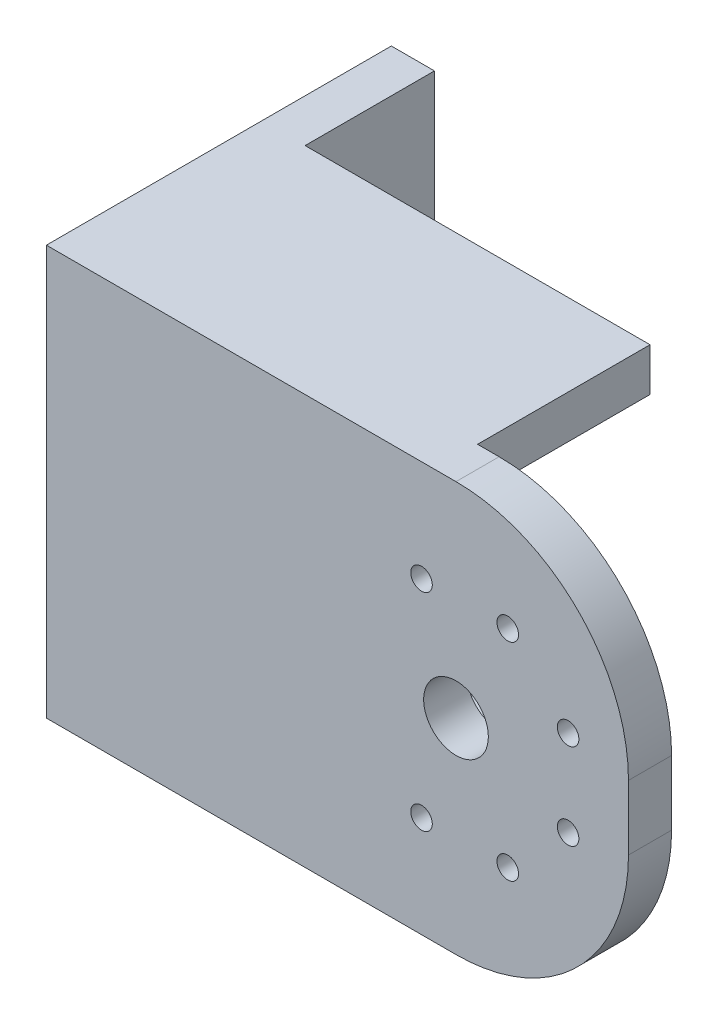
SolidWorks part; units mm, degrees
ref_plane "Front Plane" through (0, 0, 0) normal (0, 0, 1) x (1, 0, 0)
ref_plane "Top Plane" through (0, 0, 0) normal (0, 1, 0) x (1, 0, 0)
ref_plane "Right Plane" through (0, 0, 0) normal (1, 0, 0) x (0, 0, -1)
sketch "Sketch3" plane through (0, 0, 0) normal (0, 0, 1) x (1, 0, 0)
  line L6 (68.6171, 80.0599) -> (163.6171, 80.0599)
  line L10 (68.6171, 80.0599) -> (68.6171, -14.9401)
  line L36 (-101.4371, 49.8561) -> (-17.2351, 49.8561) construction
  line L70 (68.6171, -14.9401) -> (163.6171, -14.9401)
  line L71 (203.6171, 40.0599) -> (203.6171, 25.0599)
  circle A22 centre (163.6171, 32.5599) radius 7.5
  circle A23 centre (189.6171, 42.5599) radius 2.5
  circle A24 centre (155.6171, 56.5599) radius 2.5
  circle A25 centre (175.6171, 56.5599) radius 2.5
  circle A26 centre (155.6171, 8.5599) radius 2.5
  circle A27 centre (175.6171, 8.5599) radius 2.5
  circle A28 centre (189.6171, 22.5599) radius 2.5
  arc A29 (163.6171, -14.9401) -> (203.6171, 25.0599) centre (163.6171, 25.0599) ccw
  arc A30 (163.6171, 80.0599) -> (203.6171, 40.0599) centre (163.6171, 40.0599) cw
  point P23 (203.6171, 80.0599)
  dimension "D2" = 5
  dimension "D3" = 10
  dimension "D4" = 26
  dimension "D7" = 5
  dimension "D21" = 135
  dimension "D22" = 40
  dimension "D23" = 47.5
  dimension "D1" = 15
  dimension "D5" = 5
  dimension "D6" = 5
  dimension "D8" = 5
  dimension "D9" = 5
  dimension "D24" = 40
  dimension "D10" = 8
  dimension "D11" = 24
  dimension "D12" = 20
  dimension "D15" = 20
  dimension "D16" = 8
  dimension "D17" = 20
  dimension "D18" = 48
  dimension "D19" = 48
  dimension "D20" = 95
  dimension "D13" = 26
  dimension "D14" = 24
extrude "Boss-Extrude1" add sketch "Sketch3" along normal blind 10
sketch "Sketch4" plane through (0, 0, 0) normal (0, 0, -1) x (-1, 0, 0)
  line L0 (-68.6171, -14.9401) -> (-163.6171, -14.9401) construction
  line L1 (-68.6171, 80.0599) -> (-78.6171, 80.0599)
  line L2 (-68.6171, 80.0599) -> (-68.6171, -14.9401)
  line L3 (-68.6171, -14.9401) -> (-78.6171, -14.9401)
  line L4 (-78.6171, 80.0599) -> (-78.6171, -14.9401)
  dimension "D1" = 10
extrude "Boss-Extrude2" add sketch "Sketch4" along normal blind 70
sketch "Sketch5" plane through (0, 0, 0) normal (0, 0, -1) x (-1, 0, 0)
  line L1 (-78.6171, 80.0599) -> (-158.6171, 80.0599)
  line L2 (-78.6171, 80.0599) -> (-78.6171, 70.0599)
  line L3 (-78.6171, 70.0599) -> (-158.6171, 70.0599)
  line L4 (-158.6171, 80.0599) -> (-158.6171, 70.0599)
  line L5 (-78.6171, -14.9401) -> (-158.6171, -14.9401)
  line L6 (-78.6171, -14.9401) -> (-78.6171, -4.9401)
  line L7 (-78.6171, -4.9401) -> (-158.6171, -4.9401)
  line L8 (-158.6171, -14.9401) -> (-158.6171, -4.9401)
  dimension "D1" = 10
  dimension "D2" = 10
  dimension "D3" = 80
  dimension "D4" = 80
extrude "Boss-Extrude3" add sketch "Sketch5" along normal blind 40
sketch "Sketch6" plane through (0, -14.9401, 0) normal (0, -1, 0) x (1, 0, 0)
  line L0 (52.25, 0) -> (-52.25, 0) construction
  line L1 (88.6171, 0) -> (120.6171, 0)
  line L2 (88.6171, 0) -> (88.6171, -36)
  line L3 (88.6171, -36) -> (120.6171, -36)
  line L4 (120.6171, 0) -> (120.6171, -36)
  line L5 (68.6171, 10) -> (68.6171, -70) construction
  dimension "D1" = 20
  dimension "D2" = 36
  dimension "D3" = 32
extrude "Cut-Extrude1" cut sketch "Sketch6" against normal blind 43.8
fillet "Fillet2" [suppressed] radius 15
sketch "Sketch8" plane through (68.6171, 0, 0) normal (-1, 0, 0) x (0, 0, 1)
  line L0 (10, 80.0599) -> (-70, 80.0599) construction
  line L1 (-40, 32.5599) -> (-56.1679, 25.863) construction
  line L2 (-70, 32.5599) -> (0, 32.5599) construction
  line L3 (-70, -14.9401) -> (-70, 80.0599) construction
  circle A0 centre (-40, 32.5599) radius 7.5
  circle A1 centre (-56.1679, 25.863) radius 2.5
  circle A2 centre (-56.1679, 39.2569) radius 2.5
  circle A3 centre (-46.697, 48.7278) radius 2.5
  circle A4 centre (-33.303, 48.7278) radius 2.5
  circle A5 centre (-23.8321, 39.2569) radius 2.5
  circle A6 centre (-23.8321, 25.863) radius 2.5
  circle A7 centre (-33.303, 16.392) radius 2.5
  circle A8 centre (-46.697, 16.392) radius 2.5
  point P27 (-40, 32.5599)
  dimension "D1" = 15
  dimension "D6" = 5
  dimension "D2" = 47.5
  dimension "D3" = 30
  dimension "D4" = 17.5
  dimension "D5" = 22.5
  dimension "D7" = 8
extrude "Cut-Extrude2" cut sketch "Sketch8" against normal blind 43.8
fillet "Fillet3" radius 3 5 edges at (120.6171, -4.9401, -18) (120.6171, -14.9401, -18) (88.6171, -14.9401, -18) (88.6171, -4.9401, -18) (104.6171, -14.9401, 0)
